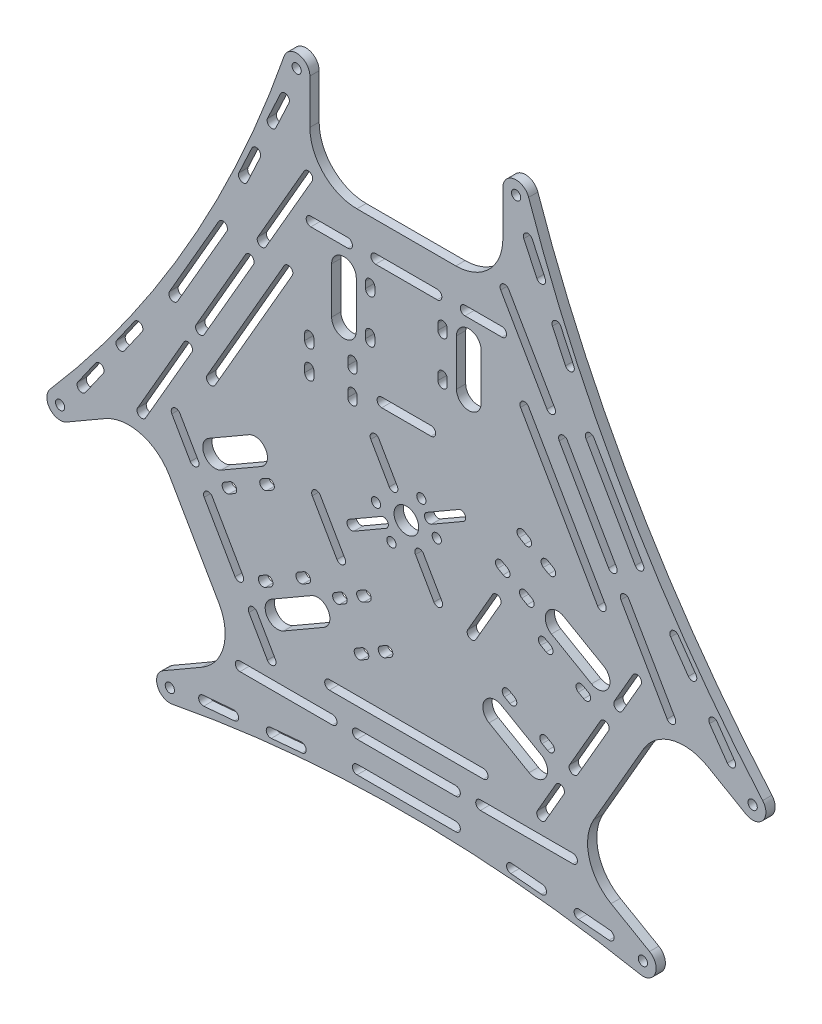
SolidWorks part; units mm, degrees
ref_plane "前视基准面" through (0, 0, 0) normal (0, 0, 1) x (1, 0, 0)
ref_plane "上视基准面" through (0, 0, 0) normal (0, 1, 0) x (1, 0, 0)
ref_plane "右视基准面" through (0, 0, 0) normal (1, 0, 0) x (0, 0, -1)
sketch "草图1" plane through (0, 0, 0) normal (0, 0, 1) x (1, 0, 0)
  line L0 (0, 123.5895) -> (0, 0) construction
  line L1 (0, 0) -> (101.6714, -58.7) construction
  line L2 (-16.05, 79.5) -> (16.05, 79.5)
  line L3 (31.3, 94.75) -> (31.3, 109.16)
  line L4 (-10, 68.46) -> (10, 68.46) construction
  line L5 (-10, 69.96) -> (10, 69.96)
  line L6 (-10, 66.96) -> (10, 66.96)
  line L7 (19, 68.46) -> (31, 68.46) construction
  line L8 (19, 69.96) -> (31, 69.96)
  line L9 (19, 66.96) -> (31, 66.96)
  line L10 (-8, 29.13) -> (8, 29.13) construction
  line L11 (-8, 30.63) -> (8, 30.63)
  line L12 (-8, 27.63) -> (8, 27.63)
  line L13 (-10.25, 17.7535) -> (-4.25, 7.3612) construction
  line L14 (-8.951, 18.5035) -> (-2.951, 8.1112)
  line L15 (-11.549, 17.0035) -> (-5.549, 6.6112)
  line L16 (17.7535, 10.25) -> (7.3612, 4.25) construction
  line L19 (18.5035, 8.951) -> (8.1112, 2.951)
  line L20 (17.0035, 11.549) -> (6.6112, 5.549)
  line L21 (10.25, -17.7535) -> (4.25, -7.3612) construction
  line L22 (8.951, -18.5035) -> (2.951, -8.1112)
  line L23 (11.549, -17.0035) -> (5.549, -6.6112)
  line L24 (-17.7535, -10.25) -> (-7.3612, -4.25) construction
  line L25 (-18.5035, -8.951) -> (-8.1112, -2.951)
  line L26 (-17.0035, -11.549) -> (-6.6112, -5.549)
  line L27 (0, 0) -> (-4, 0) construction
  line L28 (-19, 68.46) -> (-31, 68.46) construction
  line L31 (-31.5, 36) -> (-31.5, 34) construction
  line L32 (-30, 36) -> (-30, 34)
  line L33 (-33, 36) -> (-33, 34)
  line L34 (-17.5, 36) -> (-17.5, 34) construction
  line L35 (-16, 36) -> (-16, 34)
  line L36 (-19, 36) -> (-19, 34)
  line L37 (-31.5, 27) -> (-31.5, 25) construction
  line L38 (-30, 27) -> (-30, 25)
  line L39 (-33, 27) -> (-33, 25)
  line L40 (-17.5, 27) -> (-17.5, 25) construction
  line L43 (-16, 27) -> (-16, 25)
  line L44 (-19, 27) -> (-19, 25)
  line L45 (20.25, 59.96) -> (20.25, 44.96) construction
  line L48 (11.75, 60.505) -> (11.75, 58.505) construction
  line L49 (13.25, 60.505) -> (13.25, 58.505)
  line L50 (10.25, 60.505) -> (10.25, 58.505)
  line L51 (11.75, 46.415) -> (11.75, 44.415) construction
  line L52 (13.25, 46.415) -> (13.25, 44.415)
  line L53 (10.25, 46.415) -> (10.25, 44.415)
  line L54 (24.25, 59.96) -> (24.25, 44.96)
  line L55 (16.25, 59.96) -> (16.25, 44.96)
  line L56 (20.25, 52.46) -> (10.25, 52.46) construction
  line L57 (0, 0) -> (0, -126.7735) construction
  line L58 (-25, -58.7) -> (25, -58.7) construction
  line L61 (-25, -57.2) -> (25, -57.2)
  line L62 (-25, -60.2) -> (25, -60.2)
  line L63 (-16, -68) -> (16, -68) construction
  line L64 (-16, -66.5) -> (16, -66.5)
  line L65 (-16, -69.5) -> (16, -69.5)
  line L66 (24, -68) -> (54, -68) construction
  line L67 (24, -66.5) -> (54, -66.5)
  line L68 (24, -69.5) -> (54, -69.5)
  line L69 (-16, -78) -> (16, -78) construction
  line L70 (-16, -76.5) -> (16, -76.5)
  line L71 (-16, -79.5) -> (16, -79.5)
  line L72 (-31.3, 94.75) -> (-31.3, 109.16)
  line L73 (76.874, -25.8503) -> (60.824, -53.6497)
  line L74 (66.4059, -74.4816) -> (78.8853, -81.6866)
  line L75 (97.7059, -20.2684) -> (110.1853, -27.4734)
  line L76 (-60.824, -53.6497) -> (-76.874, -25.8503)
  line L77 (-97.7059, -20.2684) -> (-110.1853, -27.4734)
  line L78 (-66.4059, -74.4816) -> (-78.8853, -81.6866)
  line L79 (34, -80.8012) -> (43.9619, -81.673) construction
  line L80 (34.1308, -79.3069) -> (44.0927, -80.1787)
  line L81 (33.8692, -82.2955) -> (43.8312, -83.1673)
  line L82 (38.981, -81.2371) -> (38.6894, -84.2371) construction
  line L83 (55.9163, -82.719) -> (65.8782, -83.5908) construction
  line L84 (56.047, -81.2248) -> (66.0089, -82.0965)
  line L85 (55.7855, -84.2133) -> (65.7474, -85.0851)
  line L86 (-34, -80.8012) -> (-43.9619, -81.673) construction
  line L89 (-55.9162, -82.7191) -> (-65.8782, -83.5908) construction
  line L90 (-56.047, -81.2248) -> (-66.0089, -82.0965)
  line L91 (-55.7855, -84.2133) -> (-65.7474, -85.0851)
  line L92 (-38.3357, 51.0006) -> (-63.3357, 7.6994) construction
  line L93 (-37.0367, 50.2506) -> (-62.0367, 6.9494)
  line L94 (-39.6347, 51.7506) -> (-64.6347, 8.4494)
  line L95 (-50.8897, 47.8564) -> (-66.8897, 20.1436) construction
  line L96 (-49.5907, 47.1064) -> (-65.5907, 19.3936)
  line L97 (-52.1888, 48.6064) -> (-68.1888, 20.8936)
  line L98 (-70.8897, 13.2154) -> (-85.8897, -12.7654) construction
  line L99 (-69.5907, 12.4654) -> (-84.5907, -13.5154)
  line L100 (-72.1888, 13.9654) -> (-87.1888, -12.0154)
  line L101 (-59.55, 52.8564) -> (-75.55, 25.1436) construction
  line L102 (-58.2509, 52.1064) -> (-74.2509, 24.3936)
  line L103 (-60.849, 53.6064) -> (-76.849, 25.8936)
  line L104 (-86.9759, 10.9557) -> (-92.7118, 2.7643) construction
  line L105 (-85.7472, 10.0954) -> (-91.4831, 1.9039)
  line L106 (-88.2046, 11.8161) -> (-93.9405, 3.6247)
  line L107 (-99.5949, -7.0654) -> (-105.3308, -15.2568) construction
  line L108 (-98.3662, -7.9258) -> (-104.1021, -16.1172)
  line L109 (-100.8236, -6.205) -> (-106.5595, -14.3964)
  line L110 (-52.976, 69.8455) -> (-48.7498, 78.9086) construction
  line L111 (-51.6165, 69.2116) -> (-47.3903, 78.2747)
  line L112 (-54.3355, 70.4794) -> (-50.1093, 79.5425)
  line L113 (-43.6787, 89.7844) -> (-39.4527, 98.8476) construction
  line L114 (-42.3192, 89.1505) -> (-38.0932, 98.2137)
  line L115 (-45.0382, 90.4183) -> (-40.8121, 99.4815)
  line L116 (63.3357, 7.6994) -> (38.3357, 51.0006) construction
  line L117 (62.0366, 6.9494) -> (37.0366, 50.2506)
  line L118 (64.6347, 8.4494) -> (39.6347, 51.7506)
  line L119 (66.8897, 20.1436) -> (50.8897, 47.8564) construction
  line L120 (65.5907, 19.3936) -> (49.5907, 47.1064)
  line L121 (68.1888, 20.8936) -> (52.1888, 48.6064)
  line L122 (46.8897, 54.7846) -> (31.8897, 80.7654) construction
  line L123 (45.5907, 54.0346) -> (30.5907, 80.0154)
  line L124 (48.1888, 55.5346) -> (33.1888, 81.5154)
  line L125 (75.55, 25.1436) -> (59.55, 52.8564) construction
  line L126 (74.2509, 24.3936) -> (58.2509, 52.1064)
  line L127 (76.849, 25.8936) -> (60.849, 53.6064)
  line L128 (52.9759, 69.8455) -> (48.7499, 78.9086) construction
  line L129 (51.6164, 69.2116) -> (47.3904, 78.2747)
  line L130 (54.3354, 70.4794) -> (50.1094, 79.5425)
  line L131 (43.6787, 89.7844) -> (39.4526, 98.8476) construction
  line L132 (42.3192, 89.1505) -> (38.0932, 98.2137)
  line L133 (45.0381, 90.4183) -> (40.8121, 99.4815)
  line L134 (86.976, 10.9558) -> (92.7118, 2.7643) construction
  line L135 (85.7473, 10.0954) -> (91.483, 1.9039)
  line L136 (88.2047, 11.8162) -> (93.9405, 3.6246)
  line L137 (99.5949, -7.0654) -> (105.3308, -15.2568) construction
  line L138 (98.3662, -7.9257) -> (104.1021, -16.1172)
  line L139 (100.8236, -6.205) -> (106.5595, -14.3964)
  line L140 (39.8827, 15.0788) -> (38.1506, 16.0788)
  line L141 (38.3827, 12.4808) -> (36.6506, 13.4808)
  line L142 (32.8827, 2.9545) -> (31.1506, 3.9545)
  line L143 (31.3827, 0.3564) -> (29.6506, 1.3564)
  line L144 (27.9283, -6.8868) -> (19.9283, -20.7432)
  line L145 (30.5264, -8.3868) -> (22.5264, -22.2432)
  line L146 (40.6769, -1.5455) -> (38.9449, -0.5455)
  line L147 (39.1769, -4.1436) -> (37.4449, -3.1436)
  line L148 (47.6769, 10.5788) -> (45.9449, 11.5788)
  line L149 (46.1769, 7.9808) -> (44.4449, 8.9808)
  line L150 (43.8019, -44.0529) -> (30.8115, -36.5529)
  line L151 (39.8019, -50.9811) -> (26.8115, -43.4811)
  line L152 (35.0716, -32.0843) -> (33.3395, -31.0843)
  line L153 (33.5716, -34.6823) -> (31.8395, -33.6823)
  line L154 (47.2739, -39.1293) -> (45.5418, -38.1293)
  line L155 (45.7739, -41.7273) -> (44.0418, -40.7273)
  line L156 (70.0871, -18.5255) -> (76.0871, -8.1332)
  line L157 (67.4891, -17.0255) -> (73.4891, -6.6332)
  line L158 (62.9891, -24.8197) -> (52.9891, -42.1403)
  line L159 (65.5871, -26.3197) -> (55.5871, -43.6403)
  line L160 (48.4891, -49.9345) -> (42.4891, -60.3268)
  line L161 (51.0871, -51.4345) -> (45.0871, -61.8268)
  line L162 (64.2881, -25.5697) -> (54.2881, -42.8903) construction
  line L163 (49.7881, -50.6845) -> (43.7881, -61.0768) construction
  line L164 (29.2273, -7.6368) -> (21.2273, -21.4932) construction
  line L165 (68.7881, -17.7755) -> (74.7881, -7.3832) construction
  line L166 (46.9269, 9.2798) -> (45.1949, 10.2798) construction
  line L167 (39.9269, -2.8446) -> (38.1949, -1.8446) construction
  line L168 (39.1327, 13.7798) -> (37.4006, 14.7798) construction
  line L169 (32.1327, 1.6554) -> (30.4006, 2.6554) construction
  line L170 (46.5239, -40.4283) -> (44.7918, -39.4283) construction
  line L171 (34.3216, -33.3833) -> (32.5895, -32.3833) construction
  line L172 (41.8019, -47.517) -> (28.8115, -40.017) construction
  line L173 (-6.8827, -42.0788) -> (-5.1506, -41.0788)
  line L174 (-8.3827, -39.4808) -> (-6.6506, -38.4808)
  line L175 (-13.8827, -29.9545) -> (-12.1506, -28.9545)
  line L176 (-15.3827, -27.3564) -> (-13.6506, -26.3564)
  line L177 (-19.9283, -20.7432) -> (-27.9283, -6.8868)
  line L178 (-22.5264, -22.2432) -> (-30.5264, -8.3868)
  line L179 (-21.6769, -34.4545) -> (-19.9449, -33.4545)
  line L180 (-23.1769, -31.8564) -> (-21.4449, -30.8564)
  line L181 (-14.6769, -46.5788) -> (-12.9449, -45.5788)
  line L182 (-16.1769, -43.9808) -> (-14.4449, -42.9808)
  line L183 (-60.0519, -15.9071) -> (-47.0615, -8.4071)
  line L184 (-64.0519, -8.9789) -> (-51.0615, -1.4789)
  line L185 (-45.3216, -14.3307) -> (-43.5895, -13.3307)
  line L186 (-46.8216, -11.7327) -> (-45.0895, -10.7327)
  line L187 (-57.5239, -21.3757) -> (-55.7918, -20.3757)
  line L188 (-59.0239, -18.7777) -> (-57.2918, -17.7777)
  line L189 (-51.0871, -51.4345) -> (-45.0871, -61.8268)
  line L190 (-48.4891, -49.9345) -> (-42.4891, -60.3268)
  line L191 (-52.9891, -42.1403) -> (-62.9891, -24.8197)
  line L192 (-55.5871, -43.6403) -> (-65.5871, -26.3197)
  line L193 (-67.4891, -17.0255) -> (-73.4891, -6.6332)
  line L194 (-70.0871, -18.5255) -> (-76.0871, -8.1332)
  line L195 (-54.2881, -42.8903) -> (-64.2881, -25.5697) construction
  line L196 (-68.7881, -17.7755) -> (-74.7881, -7.3832) construction
  line L197 (-21.2273, -21.4932) -> (-29.2273, -7.6368) construction
  line L198 (-49.7881, -50.6845) -> (-43.7881, -61.0768) construction
  line L199 (-15.4269, -45.2798) -> (-13.6949, -44.2798) construction
  line L200 (-22.4269, -33.1554) -> (-20.6949, -32.1554) construction
  line L201 (-7.6327, -40.7798) -> (-5.9006, -39.7798) construction
  line L202 (-14.6327, -28.6554) -> (-12.9006, -27.6554) construction
  line L203 (-58.2739, -20.0767) -> (-56.5418, -19.0767) construction
  line L204 (-46.0716, -13.0317) -> (-44.3395, -12.0317) construction
  line L205 (-62.0519, -12.443) -> (-49.0615, -4.943) construction
  line L206 (-20.25, 59.96) -> (-20.25, 44.96) construction
  line L207 (-24.25, 59.96) -> (-24.25, 44.96)
  line L208 (-16.25, 59.96) -> (-16.25, 44.96)
  line L209 (-11.75, 46.415) -> (-11.75, 44.415) construction
  line L210 (-13.25, 46.415) -> (-13.25, 44.415)
  line L211 (-10.25, 46.415) -> (-10.25, 44.415)
  line L212 (-11.75, 60.505) -> (-11.75, 58.505) construction
  line L213 (-13.25, 60.505) -> (-13.25, 58.505)
  line L214 (-10.25, 60.505) -> (-10.25, 58.505)
  line L215 (62.0519, -12.443) -> (49.0615, -4.943) construction
  line L216 (64.0519, -8.9789) -> (51.0615, -1.4789)
  line L217 (60.0519, -15.9071) -> (47.0615, -8.4071)
  line L218 (46.0716, -13.0317) -> (44.3395, -12.0317) construction
  line L219 (46.8216, -11.7327) -> (45.0895, -10.7327)
  line L220 (45.3216, -14.3307) -> (43.5895, -13.3307)
  line L221 (58.2739, -20.0767) -> (56.5418, -19.0767) construction
  line L222 (59.0239, -18.7777) -> (57.2918, -17.7777)
  line L223 (57.5239, -21.3757) -> (55.7918, -20.3757)
  line L224 (-41.8019, -47.517) -> (-28.8115, -40.017) construction
  line L225 (-39.8019, -50.9811) -> (-26.8115, -43.4811)
  line L226 (-43.8019, -44.0529) -> (-30.8115, -36.5529)
  line L227 (-34.3216, -33.3833) -> (-32.5895, -32.3833) construction
  line L228 (-33.5716, -34.6823) -> (-31.8395, -33.6823)
  line L229 (-35.0716, -32.0843) -> (-33.3395, -31.0843)
  line L230 (-46.5239, -40.4283) -> (-44.7918, -39.4283) construction
  line L231 (-45.7739, -41.7273) -> (-44.0418, -40.7273)
  line L232 (-47.2739, -39.1293) -> (-45.5418, -38.1293)
  line L233 (-19, 69.96) -> (-31, 69.96)
  line L234 (-19, 66.96) -> (-31, 66.96)
  line L235 (-34.1307, -79.3069) -> (-44.0927, -80.1787)
  line L236 (-33.8692, -82.2955) -> (-43.8312, -83.1673)
  line L237 (-24, -68) -> (-54, -68) construction
  line L238 (-24, -66.5) -> (-54, -66.5)
  line L239 (-24, -69.5) -> (-54, -69.5)
  line L240 (-46.8897, 54.7846) -> (-31.8897, 80.7654) construction
  line L241 (-45.5907, 54.0346) -> (-30.5907, 80.0154)
  line L242 (-48.1888, 55.5346) -> (-33.1888, 81.5154)
  line L243 (70.8897, 13.2154) -> (85.8897, -12.7654) construction
  line L244 (69.5907, 12.4654) -> (84.5907, -13.5154)
  line L245 (72.1888, 13.9654) -> (87.1888, -12.0154)
  line L246 (0, 0) -> (-4.25, 7.3612) construction
  line L247 (0.0801, 9.8612) -> (-4.25, 7.3612) construction
  line L248 (-9.8612, 0.0801) -> (-7.3612, -4.25) construction
  line L249 (-7.3612, -4.25) -> (0, 0) construction
  circle A2 centre (0, 0) radius 4
  arc A3 (-10, 69.96) -> (-10, 66.96) centre (-10, 68.46) ccw
  arc A4 (10, 66.96) -> (10, 69.96) centre (10, 68.46) ccw
  arc A5 (19, 69.96) -> (19, 66.96) centre (19, 68.46) ccw
  arc A6 (31, 66.96) -> (31, 69.96) centre (31, 68.46) ccw
  arc A7 (-8, 30.63) -> (-8, 27.63) centre (-8, 29.13) ccw
  arc A8 (8, 27.63) -> (8, 30.63) centre (8, 29.13) ccw
  arc A9 (-8.951, 18.5035) -> (-11.549, 17.0035) centre (-10.25, 17.7535) ccw
  arc A10 (-5.549, 6.6112) -> (-2.951, 8.1112) centre (-4.25, 7.3612) ccw
  arc A14 (18.5035, 8.951) -> (17.0035, 11.549) centre (17.7535, 10.25) ccw
  arc A15 (6.6112, 5.549) -> (8.1112, 2.951) centre (7.3612, 4.25) ccw
  arc A16 (8.951, -18.5035) -> (11.549, -17.0035) centre (10.25, -17.7535) ccw
  arc A17 (5.549, -6.6112) -> (2.951, -8.1112) centre (4.25, -7.3612) ccw
  arc A18 (-18.5035, -8.951) -> (-17.0035, -11.549) centre (-17.7535, -10.25) ccw
  arc A19 (-6.6112, -5.549) -> (-8.1112, -2.951) centre (-7.3612, -4.25) ccw
  arc A26 (-30, 36) -> (-33, 36) centre (-31.5, 36) ccw
  arc A27 (-33, 34) -> (-30, 34) centre (-31.5, 34) ccw
  arc A28 (-16, 36) -> (-19, 36) centre (-17.5, 36) ccw
  arc A29 (-19, 34) -> (-16, 34) centre (-17.5, 34) ccw
  arc A30 (-30, 27) -> (-33, 27) centre (-31.5, 27) ccw
  arc A31 (-33, 25) -> (-30, 25) centre (-31.5, 25) ccw
  arc A34 (-16, 27) -> (-19, 27) centre (-17.5, 27) ccw
  arc A35 (-19, 25) -> (-16, 25) centre (-17.5, 25) ccw
  arc A38 (13.25, 60.505) -> (10.25, 60.505) centre (11.75, 60.505) ccw
  arc A39 (10.25, 58.505) -> (13.25, 58.505) centre (11.75, 58.505) ccw
  arc A40 (13.25, 46.415) -> (10.25, 46.415) centre (11.75, 46.415) ccw
  arc A41 (10.25, 44.415) -> (13.25, 44.415) centre (11.75, 44.415) ccw
  arc A42 (24.25, 59.96) -> (16.25, 59.96) centre (20.25, 59.96) ccw
  arc A43 (16.25, 44.96) -> (24.25, 44.96) centre (20.25, 44.96) ccw
  arc A46 (-25, -57.2) -> (-25, -60.2) centre (-25, -58.7) ccw
  arc A47 (25, -60.2) -> (25, -57.2) centre (25, -58.7) ccw
  arc A48 (-16, -66.5) -> (-16, -69.5) centre (-16, -68) ccw
  arc A49 (16, -69.5) -> (16, -66.5) centre (16, -68) ccw
  arc A50 (24, -66.5) -> (24, -69.5) centre (24, -68) ccw
  arc A51 (54, -69.5) -> (54, -66.5) centre (54, -68) ccw
  arc A52 (-16, -76.5) -> (-16, -79.5) centre (-16, -78) ccw
  arc A53 (16, -79.5) -> (16, -76.5) centre (16, -78) ccw
  arc A54 (16.05, 79.5) -> (31.3, 94.75) centre (16.05, 94.75) ccw
  circle A55 centre (35.6, 109.16) radius 4.3
  circle A56 centre (35.6, 109.16) radius 1.5
  circle A57 centre (-35.6, 109.16) radius 1.5
  circle A58 centre (-35.6, 109.16) radius 4.3
  arc A59 (-16.05, 79.5) -> (-31.3, 94.75) centre (-16.05, 94.75) cw
  arc A60 (60.824, -53.6497) -> (66.4059, -74.4816) centre (74.0309, -61.2747) ccw
  arc A61 (76.874, -25.8503) -> (97.7059, -20.2684) centre (90.0809, -33.4753) cw
  circle A62 centre (112.3353, -23.7495) radius 4.3
  circle A63 centre (112.3353, -23.7495) radius 1.5
  circle A64 centre (76.7353, -85.4105) radius 4.3
  circle A65 centre (76.7353, -85.4105) radius 1.5
  arc A66 (-76.874, -25.8503) -> (-97.7059, -20.2684) centre (-90.0809, -33.4753) ccw
  arc A67 (-60.824, -53.6497) -> (-66.4059, -74.4816) centre (-74.0309, -61.2747) cw
  circle A68 centre (-76.7353, -85.4105) radius 4.3
  circle A69 centre (-76.7353, -85.4105) radius 1.5
  circle A70 centre (-112.3353, -23.7495) radius 4.3
  circle A71 centre (-112.3353, -23.7495) radius 1.5
  arc A72 (39.6643, 110.5641) -> (115.5835, -20.9318) centre (417.7374, 241.1808) ccw
  arc A73 (75.9192, -89.6323) -> (-75.9192, -89.6323) centre (0, -482.3616) ccw
  arc A74 (-115.5835, -20.9318) -> (-39.6643, 110.5641) centre (-417.7374, 241.1808) ccw
  arc A75 (34.1308, -79.3069) -> (33.8692, -82.2955) centre (34, -80.8012) ccw
  arc A76 (43.8312, -83.1673) -> (44.0927, -80.1787) centre (43.9619, -81.673) ccw
  arc A77 (56.047, -81.2248) -> (55.7855, -84.2133) centre (55.9163, -82.719) ccw
  arc A78 (65.7474, -85.0851) -> (66.0089, -82.0965) centre (65.8782, -83.5908) ccw
  arc A81 (-56.047, -81.2248) -> (-55.7855, -84.2133) centre (-55.9162, -82.7191) cw
  arc A82 (-65.7474, -85.0851) -> (-66.0089, -82.0965) centre (-65.8782, -83.5908) cw
  arc A83 (-37.0367, 50.2506) -> (-39.6347, 51.7506) centre (-38.3357, 51.0006) ccw
  arc A84 (-64.6347, 8.4494) -> (-62.0367, 6.9494) centre (-63.3357, 7.6994) ccw
  arc A85 (-49.5907, 47.1064) -> (-52.1888, 48.6064) centre (-50.8897, 47.8564) ccw
  arc A86 (-68.1888, 20.8936) -> (-65.5907, 19.3936) centre (-66.8897, 20.1436) ccw
  arc A87 (-69.5907, 12.4654) -> (-72.1888, 13.9654) centre (-70.8897, 13.2154) ccw
  arc A88 (-87.1888, -12.0154) -> (-84.5907, -13.5154) centre (-85.8897, -12.7654) ccw
  arc A89 (-58.2509, 52.1064) -> (-60.849, 53.6064) centre (-59.55, 52.8564) ccw
  arc A90 (-76.849, 25.8936) -> (-74.2509, 24.3936) centre (-75.55, 25.1436) ccw
  arc A91 (-85.7472, 10.0954) -> (-88.2046, 11.8161) centre (-86.9759, 10.9557) ccw
  arc A92 (-93.9405, 3.6247) -> (-91.4831, 1.9039) centre (-92.7118, 2.7643) ccw
  arc A93 (-98.3662, -7.9258) -> (-100.8236, -6.205) centre (-99.5949, -7.0654) ccw
  arc A94 (-106.5595, -14.3964) -> (-104.1021, -16.1172) centre (-105.3308, -15.2568) ccw
  arc A95 (-51.6165, 69.2116) -> (-54.3355, 70.4794) centre (-52.976, 69.8455) cw
  arc A96 (-50.1093, 79.5425) -> (-47.3903, 78.2747) centre (-48.7498, 78.9086) cw
  arc A97 (-42.3192, 89.1505) -> (-45.0382, 90.4183) centre (-43.6787, 89.7844) cw
  arc A98 (-40.8121, 99.4815) -> (-38.0932, 98.2137) centre (-39.4527, 98.8476) cw
  arc A99 (62.0366, 6.9494) -> (64.6347, 8.4494) centre (63.3357, 7.6994) ccw
  arc A100 (39.6347, 51.7506) -> (37.0366, 50.2506) centre (38.3357, 51.0006) ccw
  arc A101 (65.5907, 19.3936) -> (68.1888, 20.8936) centre (66.8897, 20.1436) ccw
  arc A102 (52.1888, 48.6064) -> (49.5907, 47.1064) centre (50.8897, 47.8564) ccw
  arc A103 (45.5907, 54.0346) -> (48.1888, 55.5346) centre (46.8897, 54.7846) ccw
  arc A104 (33.1888, 81.5154) -> (30.5907, 80.0154) centre (31.8897, 80.7654) ccw
  arc A105 (74.2509, 24.3936) -> (76.849, 25.8936) centre (75.55, 25.1436) ccw
  arc A106 (60.849, 53.6064) -> (58.2509, 52.1064) centre (59.55, 52.8564) ccw
  arc A107 (51.6164, 69.2116) -> (54.3354, 70.4794) centre (52.9759, 69.8455) ccw
  arc A108 (50.1094, 79.5425) -> (47.3904, 78.2747) centre (48.7499, 78.9086) ccw
  arc A109 (42.3192, 89.1505) -> (45.0381, 90.4183) centre (43.6787, 89.7844) ccw
  arc A110 (40.8121, 99.4815) -> (38.0932, 98.2137) centre (39.4526, 98.8476) ccw
  arc A111 (85.7473, 10.0954) -> (88.2047, 11.8162) centre (86.976, 10.9558) cw
  arc A112 (93.9405, 3.6246) -> (91.483, 1.9039) centre (92.7118, 2.7643) cw
  arc A113 (98.3662, -7.9257) -> (100.8236, -6.205) centre (99.5949, -7.0654) cw
  arc A114 (106.5595, -14.3964) -> (104.1021, -16.1172) centre (105.3308, -15.2568) cw
  arc A115 (38.3827, 12.4808) -> (39.8827, 15.0788) centre (39.1327, 13.7798) ccw
  arc A116 (38.1506, 16.0788) -> (36.6506, 13.4808) centre (37.4006, 14.7798) ccw
  arc A117 (31.3827, 0.3564) -> (32.8827, 2.9545) centre (32.1327, 1.6554) ccw
  arc A118 (31.1506, 3.9545) -> (29.6506, 1.3564) centre (30.4006, 2.6554) ccw
  arc A119 (30.5264, -8.3868) -> (27.9283, -6.8868) centre (29.2273, -7.6368) ccw
  arc A120 (19.9283, -20.7432) -> (22.5264, -22.2432) centre (21.2273, -21.4932) ccw
  arc A121 (39.1769, -4.1436) -> (40.6769, -1.5455) centre (39.9269, -2.8446) ccw
  arc A122 (38.9449, -0.5455) -> (37.4449, -3.1436) centre (38.1949, -1.8446) ccw
  arc A123 (46.1769, 7.9808) -> (47.6769, 10.5788) centre (46.9269, 9.2798) ccw
  arc A124 (45.9449, 11.5788) -> (44.4449, 8.9808) centre (45.1949, 10.2798) ccw
  arc A125 (39.8019, -50.9811) -> (43.8019, -44.0529) centre (41.8019, -47.517) ccw
  arc A126 (30.8115, -36.5529) -> (26.8115, -43.4811) centre (28.8115, -40.017) ccw
  arc A127 (33.5716, -34.6823) -> (35.0716, -32.0843) centre (34.3216, -33.3833) ccw
  arc A128 (33.3395, -31.0843) -> (31.8395, -33.6823) centre (32.5895, -32.3833) ccw
  arc A129 (45.7739, -41.7273) -> (47.2739, -39.1293) centre (46.5239, -40.4283) ccw
  arc A130 (45.5418, -38.1293) -> (44.0418, -40.7273) centre (44.7918, -39.4283) ccw
  arc A131 (73.4891, -6.6332) -> (76.0871, -8.1332) centre (74.7881, -7.3832) cw
  arc A132 (70.0871, -18.5255) -> (67.4891, -17.0255) centre (68.7881, -17.7755) cw
  arc A133 (65.5871, -26.3197) -> (62.9891, -24.8197) centre (64.2881, -25.5697) ccw
  arc A134 (52.9891, -42.1403) -> (55.5871, -43.6403) centre (54.2881, -42.8903) ccw
  arc A135 (51.0871, -51.4345) -> (48.4891, -49.9345) centre (49.7881, -50.6845) ccw
  arc A136 (42.4891, -60.3268) -> (45.0871, -61.8268) centre (43.7881, -61.0768) ccw
  arc A137 (-8.3827, -39.4808) -> (-6.8827, -42.0788) centre (-7.6327, -40.7798) ccw
  arc A138 (-5.1506, -41.0788) -> (-6.6506, -38.4808) centre (-5.9006, -39.7798) ccw
  arc A139 (-15.3827, -27.3564) -> (-13.8827, -29.9545) centre (-14.6327, -28.6554) ccw
  arc A140 (-12.1506, -28.9545) -> (-13.6506, -26.3564) centre (-12.9006, -27.6554) ccw
  arc A141 (-22.5264, -22.2432) -> (-19.9283, -20.7432) centre (-21.2273, -21.4932) ccw
  arc A142 (-27.9283, -6.8868) -> (-30.5264, -8.3868) centre (-29.2273, -7.6368) ccw
  arc A143 (-23.1769, -31.8564) -> (-21.6769, -34.4545) centre (-22.4269, -33.1554) ccw
  arc A144 (-19.9449, -33.4545) -> (-21.4449, -30.8564) centre (-20.6949, -32.1554) ccw
  arc A145 (-16.1769, -43.9808) -> (-14.6769, -46.5788) centre (-15.4269, -45.2798) ccw
  arc A146 (-12.9449, -45.5788) -> (-14.4449, -42.9808) centre (-13.6949, -44.2798) ccw
  arc A147 (-64.0519, -8.9789) -> (-60.0519, -15.9071) centre (-62.0519, -12.443) ccw
  arc A148 (-47.0615, -8.4071) -> (-51.0615, -1.4789) centre (-49.0615, -4.943) ccw
  arc A149 (-46.8216, -11.7327) -> (-45.3216, -14.3307) centre (-46.0716, -13.0317) ccw
  arc A150 (-43.5895, -13.3307) -> (-45.0895, -10.7327) centre (-44.3395, -12.0317) ccw
  arc A151 (-59.0239, -18.7777) -> (-57.5239, -21.3757) centre (-58.2739, -20.0767) ccw
  arc A152 (-55.7918, -20.3757) -> (-57.2918, -17.7777) centre (-56.5418, -19.0767) ccw
  arc A153 (-42.4891, -60.3268) -> (-45.0871, -61.8268) centre (-43.7881, -61.0768) cw
  arc A154 (-51.0871, -51.4345) -> (-48.4891, -49.9345) centre (-49.7881, -50.6845) cw
  arc A155 (-55.5871, -43.6403) -> (-52.9891, -42.1403) centre (-54.2881, -42.8903) ccw
  arc A156 (-62.9891, -24.8197) -> (-65.5871, -26.3197) centre (-64.2881, -25.5697) ccw
  arc A157 (-70.0871, -18.5255) -> (-67.4891, -17.0255) centre (-68.7881, -17.7755) ccw
  arc A158 (-73.4891, -6.6332) -> (-76.0871, -8.1332) centre (-74.7881, -7.3832) ccw
  arc A159 (-24.25, 59.96) -> (-16.25, 59.96) centre (-20.25, 59.96) cw
  arc A160 (-16.25, 44.96) -> (-24.25, 44.96) centre (-20.25, 44.96) cw
  arc A161 (-13.25, 46.415) -> (-10.25, 46.415) centre (-11.75, 46.415) cw
  arc A162 (-10.25, 44.415) -> (-13.25, 44.415) centre (-11.75, 44.415) cw
  arc A163 (-13.25, 60.505) -> (-10.25, 60.505) centre (-11.75, 60.505) cw
  arc A164 (-10.25, 58.505) -> (-13.25, 58.505) centre (-11.75, 58.505) cw
  arc A165 (64.0519, -8.9789) -> (60.0519, -15.9071) centre (62.0519, -12.443) cw
  arc A166 (47.0615, -8.4071) -> (51.0615, -1.4789) centre (49.0615, -4.943) cw
  arc A167 (46.8216, -11.7327) -> (45.3216, -14.3307) centre (46.0716, -13.0317) cw
  arc A168 (43.5895, -13.3307) -> (45.0895, -10.7327) centre (44.3395, -12.0317) cw
  arc A169 (59.0239, -18.7777) -> (57.5239, -21.3757) centre (58.2739, -20.0767) cw
  arc A170 (55.7918, -20.3757) -> (57.2918, -17.7777) centre (56.5418, -19.0767) cw
  arc A171 (-39.8019, -50.9811) -> (-43.8019, -44.0529) centre (-41.8019, -47.517) cw
  arc A172 (-30.8115, -36.5529) -> (-26.8115, -43.4811) centre (-28.8115, -40.017) cw
  arc A173 (-33.5716, -34.6823) -> (-35.0716, -32.0843) centre (-34.3216, -33.3833) cw
  arc A174 (-33.3395, -31.0843) -> (-31.8395, -33.6823) centre (-32.5895, -32.3833) cw
  arc A175 (-45.7739, -41.7273) -> (-47.2739, -39.1293) centre (-46.5239, -40.4283) cw
  arc A176 (-45.5418, -38.1293) -> (-44.0418, -40.7273) centre (-44.7918, -39.4283) cw
  arc A177 (-19, 69.96) -> (-19, 66.96) centre (-19, 68.46) cw
  arc A178 (-31, 66.96) -> (-31, 69.96) centre (-31, 68.46) cw
  arc A179 (-34.1307, -79.3069) -> (-33.8692, -82.2955) centre (-34, -80.8012) cw
  arc A180 (-43.8312, -83.1673) -> (-44.0927, -80.1787) centre (-43.9619, -81.673) cw
  arc A181 (-24, -66.5) -> (-24, -69.5) centre (-24, -68) cw
  arc A182 (-54, -69.5) -> (-54, -66.5) centre (-54, -68) cw
  arc A183 (-45.5907, 54.0346) -> (-48.1888, 55.5346) centre (-46.8897, 54.7846) cw
  arc A184 (-33.1888, 81.5154) -> (-30.5907, 80.0154) centre (-31.8897, 80.7654) cw
  arc A185 (69.5907, 12.4654) -> (72.1888, 13.9654) centre (70.8897, 13.2154) cw
  arc A186 (87.1888, -12.0154) -> (84.5907, -13.5154) centre (85.8897, -12.7654) cw
  circle A189 centre (-9.8612, 0.0801) radius 1.5
  circle A190 centre (-4.8612, -8.5801) radius 1.5
  circle A191 centre (4.8612, 8.5801) radius 1.5
  circle A192 centre (9.8612, -0.0801) radius 1.5
  point P13 (0, 68.46)
  point P20 (25, 68.46)
  point P27 (0, 29.13)
  point P34 (-7.25, 12.5574)
  point P46 (12.5574, 7.25)
  point P53 (7.25, -12.5574)
  point P60 (-12.5574, -7.25)
  point P65 (0, 0)
  point P72 (-25, 68.46)
  point P79 (-31.5, 35)
  point P84 (-17.5, 35)
  point P91 (-31.5, 26)
  point P100 (-17.5, 26)
  point P107 (20.25, 52.46)
  point P112 (11.75, 59.505)
  point P119 (11.75, 45.415)
  point P131 (0, -58.7)
  point P138 (0, -68)
  point P145 (39, -68)
  point P152 (0, -78)
  point P166 (0, 79.5)
  point P196 (0, 0)
  point P206 (0, 0)
  point P207 (38.981, -81.2371)
  point P214 (60.8972, -83.1549)
  point P225 (-38.981, -81.2371)
  point P232 (-60.8972, -83.1549)
  point P238 (-20.25, 52.46)
  point P240 (-50.8357, 29.35)
  point P247 (-58.8897, 34)
  point P254 (-78.3897, 0.225)
  point P261 (-67.55, 39)
  point P268 (-89.8439, 6.86)
  point P273 (-102.4629, -11.1611)
  point P282 (-50.8629, 74.3771)
  point P289 (-41.5657, 94.316)
  point P296 (50.8357, 29.35)
  point P303 (58.8897, 34)
  point P310 (39.3897, 67.775)
  point P317 (67.55, 39)
  point P324 (50.8629, 74.3771)
  point P329 (41.5657, 94.316)
  point P338 (89.8439, 6.86)
  point P345 (102.4629, -11.1611)
  point P350 (0, 0)
  point P353 (59.2881, -34.23)
  point P360 (46.7881, -55.8806)
  point P367 (25.2273, -14.565)
  point P374 (71.7881, -12.5794)
  point P381 (46.0609, 9.7798)
  point P386 (39.0609, -2.3446)
  point P393 (38.2667, 14.2798)
  point P402 (31.2667, 2.1554)
  point P409 (35.3067, -43.767)
  point P414 (45.6578, -39.9283)
  point P421 (33.4555, -32.8833)
  point P430 (-59.2881, -34.23)
  point P437 (-71.7881, -12.5794)
  point P444 (-25.2273, -14.565)
  point P451 (-46.7881, -55.8806)
  point P458 (-14.5609, -44.7798)
  point P463 (-21.5609, -32.6554)
  point P470 (-6.7667, -40.2798)
  point P479 (-13.7667, -28.1554)
  point P486 (-55.5567, -8.693)
  point P491 (-57.4078, -19.5767)
  point P498 (-45.2055, -12.5317)
  point P505 (0, 0)
  point P512 (-11.75, 45.415)
  point P519 (-11.75, 59.505)
  point P528 (55.5567, -8.693)
  point P535 (45.2055, -12.5317)
  point P542 (57.4078, -19.5767)
  point P549 (-35.3067, -43.767)
  point P556 (-33.4555, -32.8833)
  point P563 (-45.6578, -39.9283)
  point P568 (0, 0)
  point P569 (-39, -68)
  point P578 (-39.3897, 67.775)
  point P585 (78.3897, 0.225)
  point P590 (0, 0)
  dimension "D2" = 8
  dimension "D5" = 1.5
  dimension "D15" = 8.5
  dimension "D18" = 11
  dimension "D23" = 1.5
  dimension "D25" = 4
  dimension "D31" = 1.5
  dimension "D34" = 58.7
  dimension "D33" = 1.5
  dimension "D39" = 15.25
  dimension "D41" = 29.66
  dimension "D42" = 8.6
  dimension "D43" = 3
  dimension "D45" = 800
  dimension "D47" = 1.5
  dimension "D50" = 57.2
  dimension "D57" = 5
  dimension "D16" = 8.5
  dimension "D59" = 3
  dimension "D1" = 120
  dimension "D3" = 79.5
  dimension "D4" = 31.3
  dimension "D6" = 9.54
  dimension "D7" = 20
  dimension "D8" = 9
  dimension "D9" = 12
  dimension "D10" = 36.33
  dimension "D11" = 16
  dimension "D12" = 12
  dimension "D13" = 8.5
  dimension "D14" = 17.5
  dimension "D19" = 2
  dimension "D20" = 25
  dimension "D21" = 3
  dimension "D22" = 7
  dimension "D24" = 16.25
  dimension "D26" = 15
  dimension "D27" = 3
  dimension "D28" = 2
  dimension "D29" = 12.09
  dimension "D30" = 7
  dimension "D32" = 50
  dimension "D35" = 32
  dimension "D36" = 30
  dimension "D37" = 66.5
  dimension "D38" = 8
  dimension "D40" = 10
  dimension "D48" = 3
  dimension "D49" = 10
  dimension "D51" = 10
  dimension "D52" = 12
  dimension "D54" = 3.2371
  dimension "D55" = 60
  dimension "D58" = 5
  dimension "D17" = 4
  dimension "D44" = 3
  dimension "D46" = 3
  dimension "D53" = 3
  dimension "D56" = 3
extrude "凸台-拉伸1" add sketch "草图1" along normal blind 3 contours A74 A70 L77 A66 L76 A67 L78 A68 A73 A64 L74 A60 L73 A61 L75 A62 A72 A55 L3 A54 L2 A59 L72 A58 A158 L193 A157 L194 A156 L191 A155 L192 A152 L187 A151 L188 A150 L185 A149 L186 A148 L183 A147 L184 A146 | A70 A71 | A68 A69 | A64 A65 | A62 A63 | A58 A57 | A57 | A55 A56
